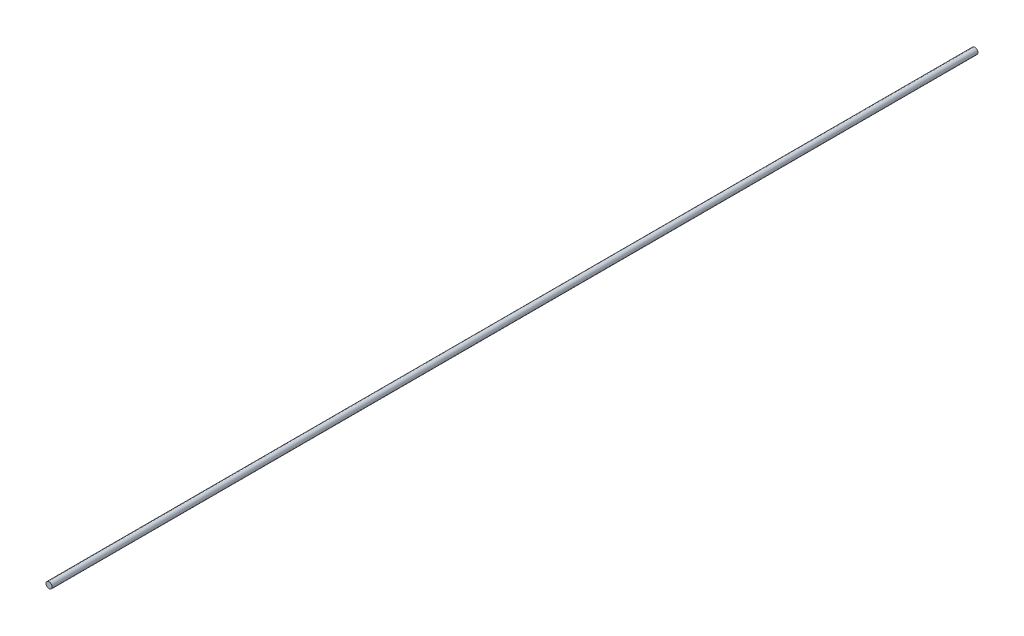
SolidWorks part; units mm, degrees
ref_plane "Front Plane" through (0, 0, 0) normal (0, 0, 1) x (1, 0, 0)
ref_plane "Top Plane" through (0, 0, 0) normal (0, 1, 0) x (1, 0, 0)
ref_plane "Right Plane" through (0, 0, 0) normal (1, 0, 0) x (0, 0, -1)
sketch "Sketch1" plane through (0, 0, 0) normal (0, 0, 1) x (1, 0, 0)
  circle A0 centre (0, 0) radius 2.5
extrude "Rod" add sketch "Sketch1" along normal blind 752
